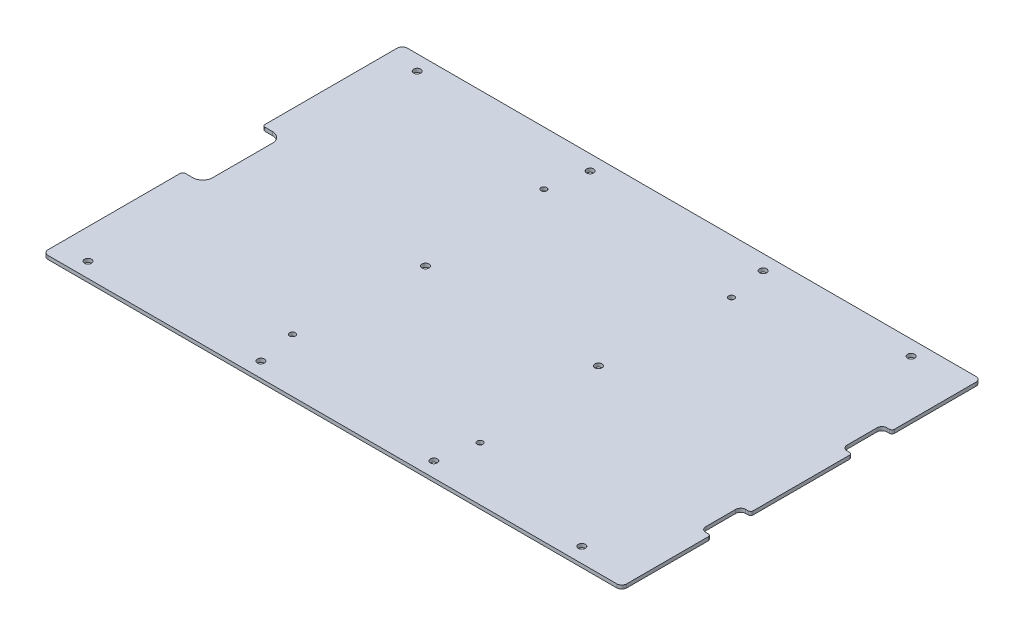
SolidWorks part; units mm, degrees
material "1060 Alloy"
ref_plane "Front" through (0, 0, 0) normal (0, 0, 1) x (1, 0, 0)
ref_plane "Top" through (0, 0, 0) normal (0, 1, 0) x (1, 0, 0)
ref_plane "Right" through (0, 0, 0) normal (1, 0, 0) x (0, 0, -1)
sketch "Sketch1" plane through (0, 0, 0) normal (0, 1, 0) x (1, 0, 0)
  line L0 (-55.0333, 0) -> (-165.1, 0) construction
  line L1 (-180.975, 114.3) -> (180.975, 114.3)
  line L2 (-184.15, 111.125) -> (-184.15, -111.125)
  line L3 (-180.975, -114.3) -> (180.975, -114.3)
  line L4 (184.15, 111.125) -> (184.15, -111.125)
  line L5 (-184.15, 114.3) -> (184.15, -114.3) construction
  line L6 (-184.15, -114.3) -> (184.15, 114.3) construction
  line L7 (-165.1, -104.775) -> (165.1, -104.775) construction
  line L8 (-165.1, -104.775) -> (-165.1, 104.775) construction
  line L9 (-165.1, 104.775) -> (165.1, 104.775) construction
  line L10 (165.1, -104.775) -> (165.1, 104.775) construction
  line L11 (-165.1, -104.775) -> (165.1, 104.775) construction
  line L12 (-165.1, 104.775) -> (165.1, -104.775) construction
  line L13 (-55.0333, -104.775) -> (55.0333, -104.775) construction
  line L14 (-55.0333, -104.775) -> (-55.0333, 104.775) construction
  line L15 (-55.0333, 104.775) -> (55.0333, 104.775) construction
  line L16 (55.0333, -104.775) -> (55.0333, 104.775) construction
  line L17 (-55.0333, -104.775) -> (55.0333, 104.775) construction
  line L18 (-55.0333, 104.775) -> (55.0333, -104.775) construction
  line L19 (55.0333, 0) -> (165.1, 0) construction
  line L20 (-55.0333, 0) -> (55.0333, 0) construction
  line L31 (-59.69, 80.01) -> (59.69, 80.01) construction
  line L32 (149.225, -104.775) -> (149.225, 104.775) construction
  line L33 (-59.69, 80.01) -> (-59.69, -80.01) construction
  line L34 (-59.69, -80.01) -> (59.69, -80.01) construction
  line L35 (59.69, 80.01) -> (59.69, -80.01) construction
  line L36 (-59.69, 80.01) -> (59.69, -80.01) construction
  line L37 (-59.69, -80.01) -> (59.69, 80.01) construction
  circle A0 centre (-165.1, 104.775) radius 2.2479
  circle A1 centre (-55.0333, 104.775) radius 2.2479
  circle A2 centre (55.0333, 104.775) radius 2.2479
  circle A3 centre (165.1, 104.775) radius 2.2479 construction
  circle A4 centre (165.1, -104.775) radius 2.2479 construction
  circle A5 centre (55.0333, -104.775) radius 2.2479
  circle A6 centre (-55.0333, -104.775) radius 2.2479
  circle A7 centre (-165.1, -104.775) radius 2.2479
  circle A12 centre (-55.0333, 0) radius 2.2479
  circle A13 centre (55.0333, 0) radius 2.2479
  arc A14 (184.15, 111.125) -> (180.975, 114.3) centre (180.975, 111.125) ccw
  arc A15 (184.15, -111.125) -> (180.975, -114.3) centre (180.975, -111.125) cw
  arc A16 (-180.975, -114.3) -> (-184.15, -111.125) centre (-180.975, -111.125) cw
  arc A17 (-180.975, 114.3) -> (-184.15, 111.125) centre (-180.975, 111.125) ccw
  circle A24 centre (149.225, -104.775) radius 2.2479
  circle A25 centre (149.225, 104.775) radius 2.2479
  circle A26 centre (59.69, -80.01) radius 1.8288
  circle A27 centre (-59.69, -80.01) radius 1.8288
  circle A28 centre (-59.69, 80.01) radius 1.8288
  circle A29 centre (59.69, 80.01) radius 1.8288
  point P0 (0, 0)
  point P6 (0, 0)
  point P11 (0, 0)
  point P28 (0, 0)
  point P29 (0, 0)
  point P32 (0, 0)
  dimension "D5" = 4.4958
  dimension "D8" = 3.6576
  dimension "D11" = 3.175
  dimension "D1" = 368.3
  dimension "D2" = 228.6
  dimension "D3" = 9.525
  dimension "D4" = 19.05
  dimension "D6" = 160.02
  dimension "D7" = 34.925
  dimension "D9" = 119.38
extrude "Boss-Extrude1" add sketch "Sketch1" along normal blind 2.286
sketch "Sketch2" plane through (0, 0, 0) normal (0, -1, 0) x (1, 0, 0)
  line L5 (184.15, 111.125) -> (184.15, -111.125) construction
  line L6 (184.15, 57.658) -> (180.975, 57.658)
  line L7 (184.15, 57.658) -> (184.15, 32.258)
  line L8 (184.15, 32.258) -> (180.975, 32.258)
  line L9 (177.8, 54.483) -> (177.8, 35.433)
  line L10 (-184.15, 0) -> (183.134, 0) construction
  line L11 (-184.15, -111.125) -> (-184.15, 111.125) construction
  line L12 (183.134, -115.824) -> (183.134, 115.824) construction
  line L13 (177.8, 44.958) -> (184.15, 44.958) construction
  line L14 (184.15, -32.258) -> (180.975, -32.258)
  line L15 (184.15, -57.658) -> (184.15, -32.258)
  line L16 (177.8, -54.483) -> (177.8, -35.433)
  line L17 (184.15, -57.658) -> (180.975, -57.658)
  line L19 (-184.15, 25.4) -> (-177.8, 25.4)
  line L20 (-184.15, 25.4) -> (-184.15, -25.4)
  line L21 (-184.15, -25.4) -> (-177.8, -25.4)
  line L22 (-171.45, 19.05) -> (-171.45, -19.05)
  arc A0 (180.975, -57.658) -> (177.8, -54.483) centre (180.975, -54.483) cw
  arc A1 (177.8, -35.433) -> (180.975, -32.258) centre (180.975, -35.433) cw
  arc A2 (177.8, 35.433) -> (180.975, 32.258) centre (180.975, 35.433) ccw
  arc A3 (177.8, 54.483) -> (180.975, 57.658) centre (180.975, 54.483) cw
  arc A4 (-171.45, -19.05) -> (-177.8, -25.4) centre (-177.8, -19.05) cw
  arc A5 (-171.45, 19.05) -> (-177.8, 25.4) centre (-177.8, 19.05) ccw
  point P20 (177.8, -57.658)
  point P23 (177.8, -32.258)
  point P26 (177.8, 32.258)
  point P29 (177.8, 57.658)
  point P38 (-171.45, 25.4)
  dimension "D4" = 3.175
  dimension "D7" = 6.35
  dimension "D1" = 25.4
  dimension "D2" = 44.958
  dimension "D3" = 6.35
  dimension "D5" = 50.8
  dimension "D6" = 12.7
extrude "Cut-Extrude1" cut sketch "Sketch2" against normal through all
fillet "Fillet1" radius 1.5875 6 edges at (184.15, 1.143, -57.658) (184.15, 1.143, -32.258) (184.15, 1.143, 32.258) (184.15, 1.143, 57.658) (-184.15, 1.143, -25.4) (-184.15, 1.143, 25.4)
